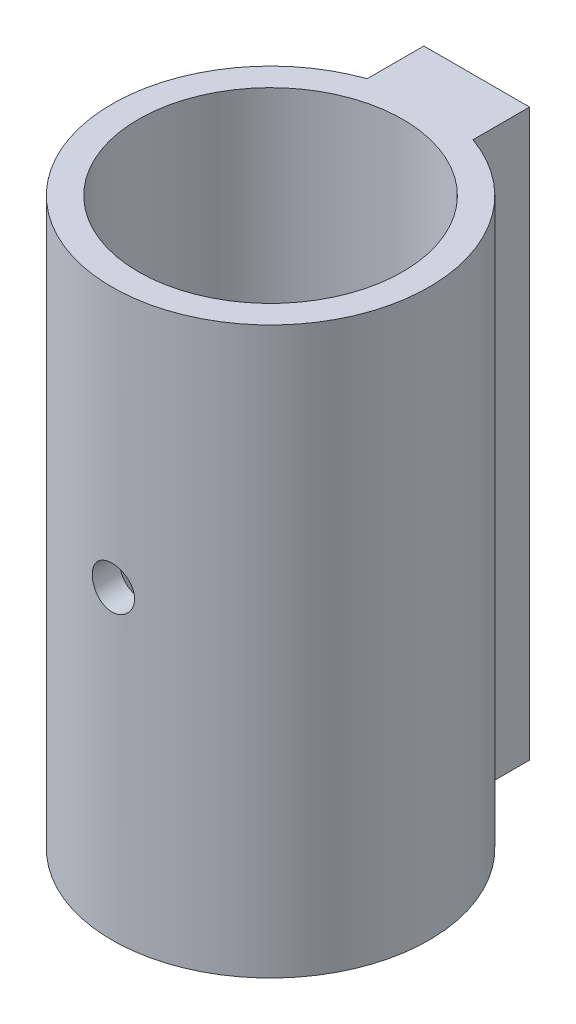
SolidWorks part; units mm, degrees
ref_plane "Front Plane" through (0, 0, 0) normal (0, 0, 1) x (1, 0, 0)
ref_plane "Top Plane" through (0, 0, 0) normal (0, 1, 0) x (1, 0, 0)
ref_plane "Right Plane" through (0, 0, 0) normal (1, 0, 0) x (0, 0, -1)
sketch "Sketch2" plane through (0, 0, 0) normal (0, 1, 0) x (1, 0, 0)
  line L0 (0, 7.8) -> (-2, 7.8)
  line L1 (-2, 7.8) -> (-2, 5.6569)
  line L2 (0, 7.8) -> (2, 7.8)
  line L3 (2, 7.8) -> (2, 5.6569)
  line L4 (-2.5415, -6) -> (44.0386, -6) construction
  line L5 (0, 0) -> (0, 7.8) construction
  arc A0 (-2, 5.6569) -> (2, 5.6569) centre (0, 0) ccw
  point P9 (0.08, 7.4438)
  dimension "D1" = 6
  dimension "D2" = 4
  dimension "D3" = 13.8
extrude "Boss-Extrude1" add sketch "Sketch2" along normal blind 21.4
sketch "Sketch3" plane through (0, 21.4, 0) normal (0, 1, 0) x (1, 0, 0)
  circle A0 centre (0, 0) radius 5
  dimension "D1" = 10
extrude "Cut-Extrude1" cut sketch "Sketch3" against normal blind 24.9
sketch "Sketch4" plane through (0, 0, -7.8) normal (0, 0, -1) x (-1, 0, 0)
  line L0 (0, 21.4) -> (0, 0) construction
  line L1 (-2, 21.4) -> (2, 21.4) construction
  circle A0 centre (0, 11.5544) radius 1.99
  dimension "D1" = 3.98
extrude "Cut-Extrude2" cut sketch "Sketch4" against normal blind 2
sketch "Sketch5" plane through (0, 0, -5.8) normal (0, 0, -1) x (-1, 0, 0)
  circle A0 centre (0, 11.5544) radius 0.8
  dimension "D1" = 1.6
extrude "Cut-Extrude3" cut sketch "Sketch5" against normal through all
